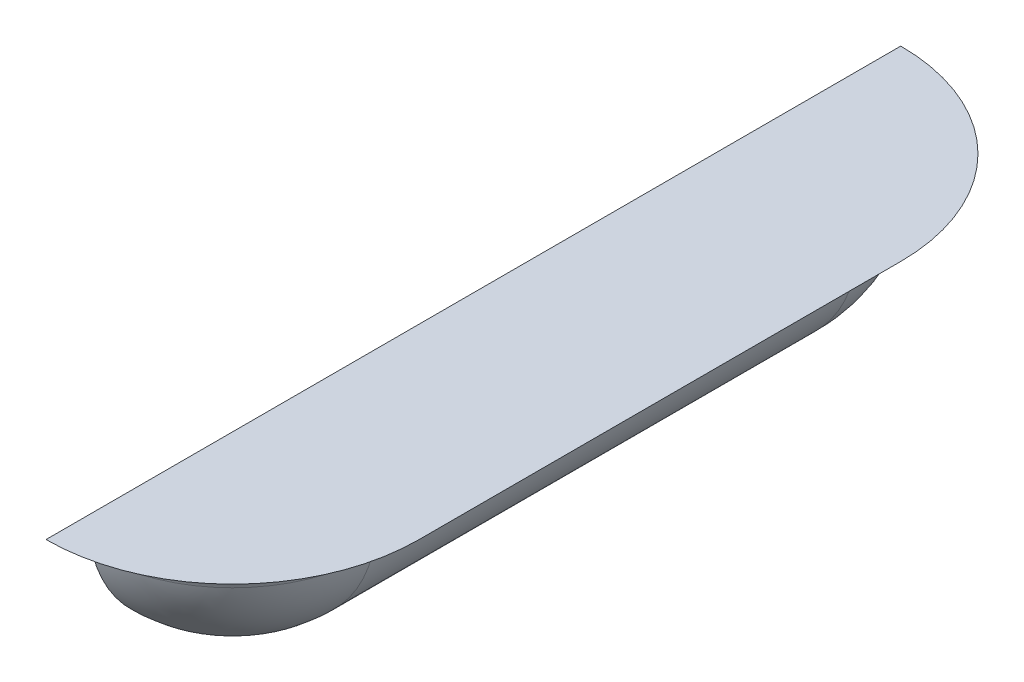
SolidWorks part; units mm, degrees
ref_plane "Plane1" through (0, 0, 0) normal (0, 0, 1) x (1, 0, 0)
ref_plane "Plane2" through (0, 0, 0) normal (0, 1, 0) x (1, 0, 0)
ref_plane "Plane3" through (0, 0, 0) normal (1, 0, 0) x (0, 0, -1)
sketch "Sketch1" plane through (0, 0, 0) normal (0, 0, 1) x (1, 0, 0)
  line L0 (-15, 0) -> (15, 0)
  line L1 (-15, 0) -> (-15, 3.4642)
  line L2 (15, 3.4642) -> (-15, 3.4642)
  line L3 (15, 3.4642) -> (15, 0)
  line L4 (0, 0) -> (0, 3.4642) construction
  line L5 (50, 0) -> (-50, 0) construction
  dimension "D1" = 30
extrude "Base-Extrude" add sketch "Sketch1" along normal mid plane 50
sketch "Layout Sketch" plane through (0, 0, 0) normal (0, -1, 0) x (1, 0, 0)
  line L0 (-6.5173, 0) -> (7.2244, 0) construction
  line L1 (11.2638, 0) -> (-11.2638, 0) construction
  line L2 (0, 9.1132) -> (0, -7.6236) construction
  line L3 (0, -50) -> (0, 50) construction
  line L9 (-3, -16) -> (-3, 16)
  line L11 (3, 10) -> (3, -10)
  arc A0 (3, 10) -> (-3, 16) centre (-3, 10) ccw
  arc A1 (3, -10) -> (-3, -16) centre (-3, -10) cw
  dimension "Overall width" = 32
  dimension "Depth" = 6
sketch "Louver Body" plane through (0, 0, 0) normal (0, 0, 1) x (1, 0, 0)
  line L0 (-3, 0) -> (-3, -6)
  line L1 (-15, 0) -> (15, 0) construction
  line L2 (-3, 0) -> (3, 0)
  line L4 (3, 0) -> (3, 3.4642) construction
  line L5 (15, 3.4642) -> (-15, 3.4642) construction
  line L6 (-3, -6) -> (-3.0249, -6) construction
  line L8 (0, 3.4642) -> (0, 0) construction
  arc A0 (-3, -6) -> (3, 0) centre (-3, 0) ccw
extrude "Boss-Extrude1" add sketch "Louver Body" along normal mid plane 20
sketch "Sketch12" plane through (0, 0, 10) normal (0, 0, 1) x (1, 0, 0)
  line L0 (-3, 0) -> (-3, -6) construction
  line L1 (-3, 0) -> (-3, -6) construction
  line L2 (-15, 0) -> (15, 0) construction
  line L5 (3, 0) -> (-3, 0)
  line L6 (-3, 0) -> (-3, -6)
  line L7 (3, 0) -> (-3, 0)
  line L8 (-3, 0) -> (-3, -6)
  arc A0 (-3, -6) -> (3, 0) centre (-3, 0) ccw construction
  arc A2 (-3, -6) -> (3, 0) centre (-3, 0) ccw
  arc A3 (-3, -6) -> (3, 0) centre (-3, 0) ccw
  dimension "D1" = 0
revolve "Boss-Revolve2" add sketch "Sketch12" angle 90 about L1
sketch "Sketch13" plane through (0, 0, -10) normal (0, 0, -1) x (-1, 0, 0)
  line L0 (3, -6) -> (3, 0) construction
  line L1 (15, 0) -> (-15, 0) construction
  line L2 (3, 0) -> (-3, 0)
  line L3 (3, -6) -> (3, 0)
  line L4 (3, 0) -> (-3, 0)
  line L5 (3, -6) -> (3, 0)
  arc A1 (-3, 0) -> (3, -6) centre (3, 0) ccw
  arc A2 (-3, 0) -> (3, -6) centre (3, 0) ccw
  dimension "D1" = 0
revolve "Boss-Revolve3" add sketch "Sketch13" angle 90 about L0
fillet "Fillet1" radius 2 3 edges at (1.2426, 0, 14.2426) (3, 0, 0) (1.2426, 0, -14.2426)
sketch "Sketch8" plane through (-15, 0, 0) normal (-1, 0, 0) x (0, 0, 1)
  line L4 (-25, 0) -> (25, 0)
  line L5 (25, 0) -> (25, 3.4642)
  line L6 (25, 3.4642) -> (-25, 3.4642)
  line L7 (-25, 3.4642) -> (-25, 0)
  line L8 (-25, 0) -> (25, 0)
  line L9 (25, 0) -> (25, 3.4642)
  line L10 (25, 3.4642) -> (-25, 3.4642)
  line L11 (-25, 3.4642) -> (-25, 0)
  dimension "D1" = 0
extrude "Cut-Extrude4" cut sketch "Sketch8" against normal through all
sketch "Orientation sketch" plane through (0, 0, 0) normal (0, 1, 0) x (-1, 0, 0)
  line L2 (3, 17.746) -> (3, -17.746)
  line L3 (3, 17.746) -> (3, -17.746)
  line L4 (-4.746, 10) -> (-4.746, -10)
  line L5 (-4.746, 10) -> (-4.746, -10)
  arc A2 (3, 17.746) -> (-4.746, 10) centre (3, 10) ccw
  arc A3 (3, 17.746) -> (-4.746, 10) centre (3, 10) ccw
  arc A4 (-4.746, -10) -> (3, -17.746) centre (3, -10) ccw
  arc A5 (-4.746, -10) -> (3, -17.746) centre (3, -10) ccw
  dimension "D1" = 0
equation "\"Width@Boss-Extrude1\"=\"Overall width@Layout Sketch\"-2*\"Depth@Layout Sketch\""
